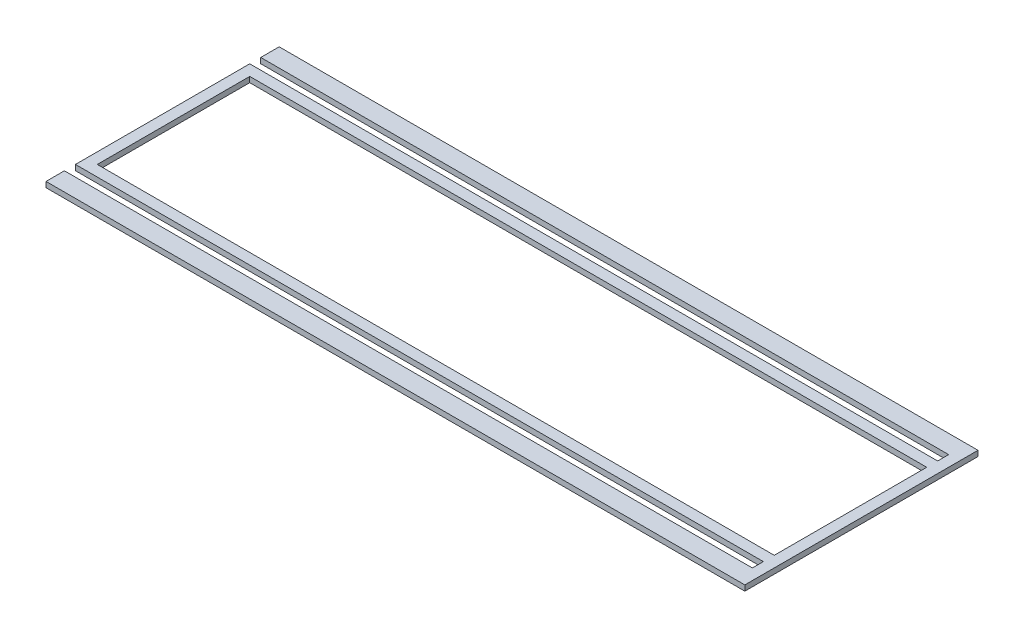
SolidWorks part; units mm, degrees
ref_plane "Front Plane" through (0, 0, 0) normal (0, 0, 1) x (1, 0, 0)
ref_plane "Top Plane" through (0, 0, 0) normal (0, 1, 0) x (1, 0, 0)
ref_plane "Right Plane" through (0, 0, 0) normal (1, 0, 0) x (0, 0, -1)
sketch "Sketch1" plane through (0, 0, 0) normal (0, 1, 0) x (1, 0, 0)
  line L0 (-203.2, 50.6794) -> (-203.2, -50.6793)
  line L1 (-203.2, 67.7958) -> (203.2, 67.7958)
  line L2 (-203.2, 67.7958) -> (-203.2, 57.0802)
  line L3 (-203.2, -67.7958) -> (203.2, -67.7958)
  line L4 (203.2, 67.7958) -> (203.2, -67.7958)
  line L5 (-203.2, 67.7958) -> (203.2, -67.7958) construction
  line L6 (-203.2, -67.7958) -> (203.2, 67.7958) construction
  line L7 (-203.2, -67.7958) -> (190.5, -67.7958)
  line L8 (-203.2, -67.7958) -> (-203.2, -57.0801)
  line L9 (-203.2, -57.0801) -> (196.85, -57.0801)
  line L11 (-203.2, 67.7958) -> (190.5, 67.7958)
  line L12 (-203.2, 67.7958) -> (-203.2, 57.0802)
  line L13 (-203.2, 57.0802) -> (196.85, 57.0802)
  line L15 (-203.2, -57.0801) -> (196.85, -57.0801)
  line L17 (-203.2, -50.6793) -> (196.85, -50.6793)
  line L18 (196.85, -57.0801) -> (196.85, -50.6793)
  line L19 (-203.2, 57.0802) -> (196.85, 57.0802)
  line L21 (-203.2, 50.6794) -> (196.85, 50.6794)
  line L22 (196.85, 57.0802) -> (196.85, 50.6794)
  line L23 (-203.2, -57.0801) -> (-203.2, -67.7958)
  line L25 (-196.85, -44.3293) -> (196.85, -44.3293)
  line L26 (-196.85, -44.3293) -> (-196.85, 44.3294)
  line L27 (-196.85, 44.3294) -> (196.85, 44.3294)
  line L28 (196.85, -44.3293) -> (196.85, 44.3294)
  line L29 (-196.85, -44.3293) -> (196.85, 44.3294) construction
  line L30 (-196.85, 44.3294) -> (196.85, -44.3293) construction
  point P0 (0, 0)
  point P16 (0, 0)
  dimension "D1" = 406.4
  dimension "D2" = 135.5915
  dimension "D4" = 10.7156
  dimension "D5" = 10.7156
  dimension "D6" = 6.4008
  dimension "D7" = 6.4008
  dimension "D3" = 6.35
  dimension "D8" = 6.35
  dimension "D9" = 6.35
  dimension "D10" = 6.35
extrude "Boss-Extrude1" add sketch "Sketch1" along normal mid plane 3.175 contours L1 L13 L2 L9 L3 L4 region at (-3.175, 0, -46.3951)
equation "\"D2@Sketch1\"      = 5.698in-(1*(2*0.125in))-(2*3/64) - (2*0.008)"
equation "\"D1@Sketch1\"=16.00in"
equation "\"D6@Sketch1\"=0.252"
